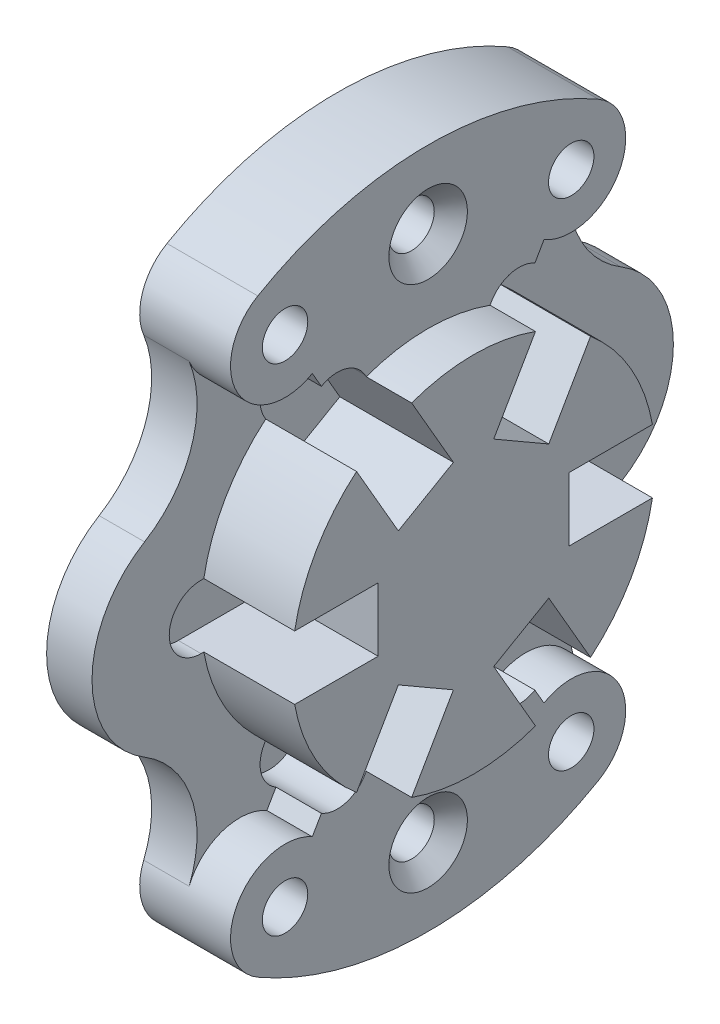
SolidWorks part; units mm, degrees
material "Beryllium Copper, UNS C17000"
ref_plane "Front Plane" through (0, 0, 0) normal (0, 0, 1) x (1, 0, 0)
ref_plane "Top Plane" through (0, 0, 0) normal (0, 1, 0) x (1, 0, 0)
ref_plane "Right Plane" through (0, 0, 0) normal (1, 0, 0) x (0, 0, -1)
sketch "Sketch1" plane through (0, 0, 0) normal (1, 0, 0) x (0, 0, -1)
  line L0 (21, 7) -> (40, 7)
  line L1 (40, -7) -> (21, -7)
  line L2 (21, 7) -> (21, -7)
  line L3 (16.5622, -14.6865) -> (4.4378, -21.6865)
  line L4 (13.9378, -38.141) -> (4.4378, -21.6865)
  line L5 (16.5622, -14.6865) -> (26.0622, -31.141)
  line L6 (-4.4378, -21.6865) -> (-16.5622, -14.6865)
  line L7 (-26.0622, -31.141) -> (-16.5622, -14.6865)
  line L8 (-4.4378, -21.6865) -> (-13.9378, -38.141)
  line L9 (-21, -7) -> (-21, 7)
  line L10 (-40, 7) -> (-21, 7)
  line L11 (-21, -7) -> (-40, -7)
  line L12 (-16.5622, 14.6865) -> (-4.4378, 21.6865)
  line L13 (-13.9378, 38.141) -> (-4.4378, 21.6865)
  line L14 (-16.5622, 14.6865) -> (-26.0622, 31.141)
  line L15 (4.4378, 21.6865) -> (16.5622, 14.6865)
  line L16 (26.0622, 31.141) -> (16.5622, 14.6865)
  line L17 (4.4378, 21.6865) -> (13.9378, 38.141)
  line L18 (-31.5, 54.5596) -> (0, 0) construction
  line L19 (0, 0) -> (31.5, 54.5596) construction
  line L20 (25.5, 44.1673) -> (23.5, 40.7032)
  line L21 (-25.5, 44.1673) -> (-23.5, 40.7032)
  line L22 (69.3, 0) -> (-69.3, 0) construction
  line L23 (-25.5, -44.1673) -> (-23.5, -40.7032)
  line L24 (25.5, -44.1673) -> (23.5, -40.7032)
  line L25 (0, 75.9) -> (0, -75.9) construction
  arc A0 (-39.3827, -7) -> (-25.7535, -30.6065) centre (0, 0) ccw
  circle A1 centre (0, 0) radius 63 construction
  arc A2 (40, 7) -> (40, -7) centre (40, 0) cw
  arc A3 (-39.3827, -7) -> (-25.7535, -30.6065) centre (0, 0) ccw
  arc A4 (26.0622, -31.141) -> (13.9378, -38.141) centre (20, -34.641) cw
  arc A5 (-39.3827, -7) -> (-25.7535, -30.6065) centre (0, 0) ccw
  arc A6 (-13.9378, -38.141) -> (-26.0622, -31.141) centre (-20, -34.641) cw
  arc A7 (-39.3827, -7) -> (-25.7535, -30.6065) centre (0, 0) ccw
  arc A8 (-40, -7) -> (-40, 7) centre (-40, 0) cw
  arc A9 (-39.3827, -7) -> (-25.7535, -30.6065) centre (0, 0) ccw
  arc A10 (-26.0622, 31.141) -> (-13.9378, 38.141) centre (-20, 34.641) cw
  arc A11 (-39.3827, -7) -> (-25.7535, -30.6065) centre (0, 0) ccw
  arc A12 (13.9378, 38.141) -> (26.0622, 31.141) centre (20, 34.641) cw
  arc A13 (-25.7535, 30.6065) -> (-39.3827, 7) centre (0, 0) ccw
  arc A14 (-25.7535, 30.6065) -> (-39.3827, 7) centre (0, 0) ccw
  arc A15 (-25.7535, 30.6065) -> (-39.3827, 7) centre (0, 0) ccw
  arc A16 (-25.7535, 30.6065) -> (-39.3827, 7) centre (0, 0) ccw
  arc A17 (-25.7535, 30.6065) -> (-39.3827, 7) centre (0, 0) ccw
  arc A18 (-25.7535, 30.6065) -> (-39.3827, 7) centre (0, 0) ccw
  arc A19 (13.6292, 37.6065) -> (-13.6292, 37.6065) centre (0, 0) ccw
  arc A20 (13.6292, 37.6065) -> (-13.6292, 37.6065) centre (0, 0) ccw
  arc A21 (13.6292, 37.6065) -> (-13.6292, 37.6065) centre (0, 0) ccw
  arc A22 (13.6292, 37.6065) -> (-13.6292, 37.6065) centre (0, 0) ccw
  arc A23 (13.6292, 37.6065) -> (-13.6292, 37.6065) centre (0, 0) ccw
  arc A24 (13.6292, 37.6065) -> (-13.6292, 37.6065) centre (0, 0) ccw
  arc A25 (39.3827, 7) -> (25.7535, 30.6065) centre (0, 0) ccw
  arc A26 (39.3827, 7) -> (25.7535, 30.6065) centre (0, 0) ccw
  arc A27 (39.3827, 7) -> (25.7535, 30.6065) centre (0, 0) ccw
  arc A28 (39.3827, 7) -> (25.7535, 30.6065) centre (0, 0) ccw
  arc A29 (39.3827, 7) -> (25.7535, 30.6065) centre (0, 0) ccw
  arc A30 (39.3827, 7) -> (25.7535, 30.6065) centre (0, 0) ccw
  arc A31 (25.7535, -30.6065) -> (39.3827, -7) centre (0, 0) ccw
  arc A32 (25.7535, -30.6065) -> (39.3827, -7) centre (0, 0) ccw
  arc A33 (25.7535, -30.6065) -> (39.3827, -7) centre (0, 0) ccw
  arc A34 (25.7535, -30.6065) -> (39.3827, -7) centre (0, 0) ccw
  arc A35 (25.7535, -30.6065) -> (39.3827, -7) centre (0, 0) ccw
  arc A36 (25.7535, -30.6065) -> (39.3827, -7) centre (0, 0) ccw
  arc A37 (-13.6292, -37.6065) -> (13.6292, -37.6065) centre (0, 0) ccw
  arc A38 (-13.6292, -37.6065) -> (13.6292, -37.6065) centre (0, 0) ccw
  arc A39 (-13.6292, -37.6065) -> (13.6292, -37.6065) centre (0, 0) ccw
  arc A40 (-13.6292, -37.6065) -> (13.6292, -37.6065) centre (0, 0) ccw
  arc A41 (-13.6292, -37.6065) -> (13.6292, -37.6065) centre (0, 0) ccw
  arc A42 (-13.6292, -37.6065) -> (13.6292, -37.6065) centre (0, 0) ccw
  arc A43 (-31.5, 54.5596) -> (31.5, 54.5596) centre (0, 0) cw construction
  arc A44 (37.5, 64.9519) -> (-37.5, 64.9519) centre (0, 0) ccw
  arc A46 (25.5, 44.1673) -> (37.5, 64.9519) centre (31.5, 54.5596) ccw
  arc A47 (-37.5, 64.9519) -> (-25.5, 44.1673) centre (-31.5, 54.5596) ccw
  circle A48 centre (31.5, 54.5596) radius 5
  circle A49 centre (-31.5, 54.5596) radius 5
  circle A50 centre (0, 58) radius 5
  arc A51 (42.6236, 50.0578) -> (52.4354, 20.5271) centre (64.8707, 41.0542) ccw
  arc A52 (52.4354, 20.5271) -> (52.4354, -20.5271) centre (40, 0) cw
  arc A53 (-37.5, -64.9519) -> (-25.5, -44.1673) centre (-31.5, -54.5596) cw
  circle A54 centre (-31.5, -54.5596) radius 5
  circle A55 centre (0, -58) radius 5
  arc A56 (37.5, -64.9519) -> (-37.5, -64.9519) centre (0, 0) cw
  circle A57 centre (31.5, -54.5596) radius 5
  arc A58 (25.5, -44.1673) -> (37.5, -64.9519) centre (31.5, -54.5596) cw
  arc A59 (42.6236, -50.0578) -> (52.4354, -20.5271) centre (64.8707, -41.0542) cw
  arc A60 (-42.6236, -50.0578) -> (-52.4354, -20.5271) centre (-64.8707, -41.0542) ccw
  arc A61 (-42.6236, 50.0578) -> (-52.4354, 20.5271) centre (-64.8707, 41.0542) cw
  arc A62 (-52.4354, 20.5271) -> (-52.4354, -20.5271) centre (-40, 0) ccw
  point P8 (21, 0)
  point P54 (0, 63)
  point P62 (0, 75)
  point P71 (-40.7305, 0)
  dimension "D1" = 7
  dimension "D3" = 80
  dimension "D4" = 126
  dimension "D7" = 75
  dimension "D8" = 10
  dimension "D9" = 10
  dimension "D11" = 24
  dimension "D2" = 21
  dimension "D6" = 60
  dimension "D10" = 58
  dimension "D5" = 6
extrude "Boss-Extrude1" add sketch "Sketch1" along normal blind 10 contours A61 A62 A60 A53 L23 A6 L7 A0 L11 A8 L10 A13 L14 A10 L21 A47 | A58 A59 A52 A51 A46 L20 A12 L16 A25 L0 A2 L1 A31 L5 A4 L24 region at (0, 20.54, -35.5763) region at (0, 36.7323, 27.8047)
extrude "Boss-Extrude2" add sketch "Sketch1<3>" along normal blind 30 contours L8 A37 L4 L3 L5 A31 L1 L2 L0 A25 L16 L15 L17 A19 L13 L12 L14 A13 L10 L9 L11 A0 L7 L6 region at (0, 0, 0)
sketch "Sketch1<3>" plane through (0, 0, 0) normal (1, 0, 0) x (0, 0, -1) same geometry as "Sketch1"
extrude "Boss-Extrude3" add sketch "Sketch1<4>" along normal blind 5 contours A12 L17 L15 L16 | A10 L14 L12 L13 | A2 L0 L2 L1 | A8 L11 L9 L10 | A6 L8 L6 L7 | A4 L5 L3 L4 region at (0, 0, -33.2987) region at (0, 28.8375, -16.6494) region at (0, -28.8375, -16.6494) region at (0, 28.8375, 16.6494) region at (0, -28.8375, 16.6494) region at (0, 0, 33.2987)
sketch "Sketch1<4>" plane through (0, 0, 0) normal (1, 0, 0) x (0, 0, -1) same geometry as "Sketch1"
extrude "Boss-Extrude4" add sketch "Sketch1<5>" along normal blind 20 contours A44 A47 L21 A10 L13 A19 L17 A12 L20 A46 A50 A49 A48 | A58 L24 A4 L4 A37 L8 A6 L23 A53 A56 A55 A54 A57 region at (0, 42.3172, -17.9432) region at (0, -42.9087, -23.6799)
sketch "Sketch1<5>" plane through (0, 0, 0) normal (1, 0, 0) x (0, 0, -1) same geometry as "Sketch1"
hole_wizard "CSK for M8 Flat Head Machine Screw1" positions "Sketch2" profile "Sketch3" countersink size "M8" standard "ANSI Metric" end condition through all
sketch "Sketch2" plane through (20, 0, 0) normal (1, 0, 0) x (0, 0, -1)
  point P0 (0, 58)
  point P3 (0, -58)
sketch "Sketch3" plane through (20, 58, 0) normal (0, 1, 0) x (0, 0, -1)
  line L0 (0, 0) -> (0, 20)
  line L1 (0, 20) -> (5, 20)
  line L2 (5, 20) -> (5, 3.65)
  line L3 (5, 3.65) -> (8.65, 0)
  line L5 (8.65, 0) -> (0, 0)
  line L6 (-5, 3.65) -> (-8.65, 0) construction
  line L11 (0, -6.35) -> (0, 107.95) construction
  dimension "Thru Hole Dia." = 10
  dimension "Thru Hole Depth" = 20
  dimension "Near C'Sink Dia." = 17.3
  dimension "Near C'Sink Angle" = 90
